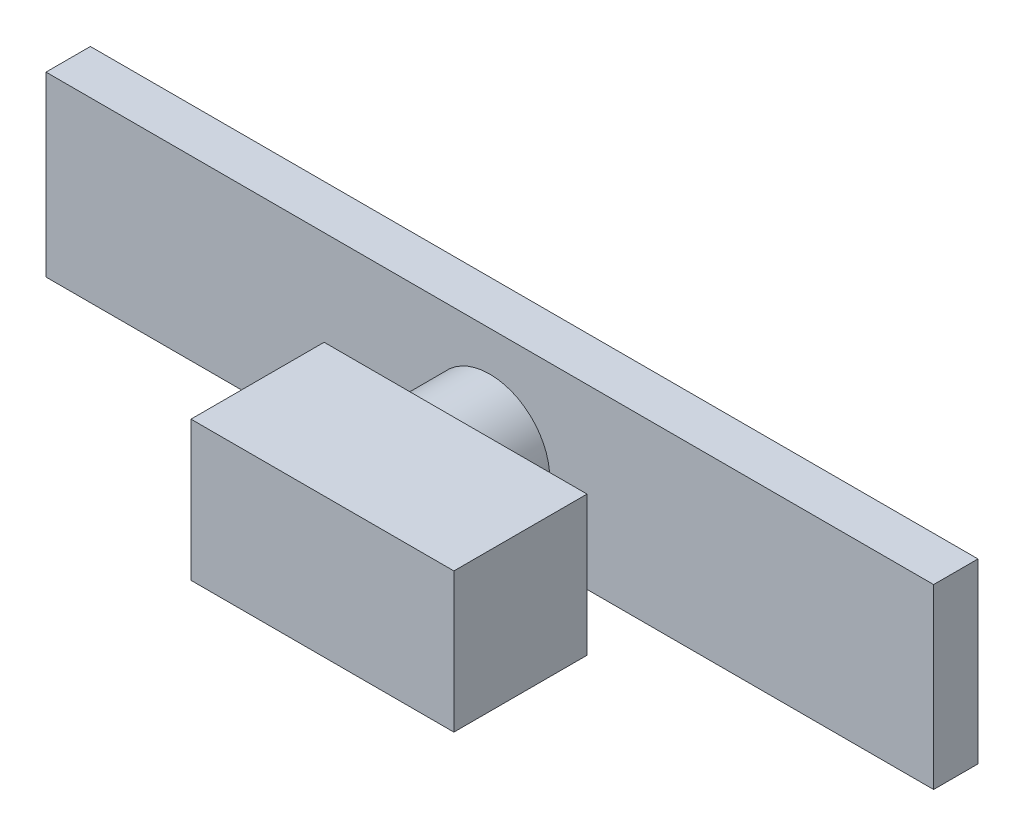
SolidWorks part; units mm, degrees
ref_plane "Front Plane" through (0, 0, 0) normal (0, 0, 1) x (1, 0, 0)
ref_plane "Top Plane" through (0, 0, 0) normal (0, 1, 0) x (1, 0, 0)
ref_plane "Right Plane" through (0, 0, 0) normal (1, 0, 0) x (0, 0, -1)
sketch "Sketch2" plane through (0, 0, 0) normal (0, 0, 1) x (1, 0, 0)
  line L1 (-47.8692, 21.2481) -> (206.1308, 21.2481)
  line L2 (-47.8692, 21.2481) -> (-47.8692, 8.5481)
  line L3 (-47.8692, 8.5481) -> (206.1308, 8.5481)
  line L4 (206.1308, 21.2481) -> (206.1308, 8.5481)
  dimension "D1" = 12.7
  dimension "D2" = 254
extrude "Boss-Extrude1" add sketch "Sketch2" along normal blind 50.8
sketch "Sketch3" plane through (0, 21.2481, 0) normal (0, 1, 0) x (1, 0, 0)
  circle A0 centre (79.1308, -28.4831) radius 17.1408
extrude "Boss-Extrude2" add sketch "Sketch3" along normal blind 19.05
sketch "Sketch4" plane through (0, 40.2981, 0) normal (0, 1, 0) x (1, 0, 0)
  line L1 (50.7675, -8.111) -> (126.0034, -8.111)
  line L2 (50.7675, -8.111) -> (50.7675, -48.0661)
  line L3 (50.7675, -48.0661) -> (126.0034, -48.0661)
  line L4 (126.0034, -8.111) -> (126.0034, -48.0661)
extrude "Boss-Extrude3" add sketch "Sketch4" along normal blind 38.1
scale "Scale2" scale about centroid uniform scaling yes scale factor 0.06
move or copy body "Body-Move/Copy1" bodies to move or copy 105 copy no rotation origin (0, 33.6669, 26.5501) rotation axis (1, 0, 0) rotation angle 90
move or copy body "Body-Move/Copy3" bodies to move or copy 106 copy no translate (-50.8, 0, -50.8)
scale "Scale5" scale about centroid uniform scaling yes scale factor 0.25
move or copy body "Body-Move/Copy9" bodies to move or copy 111 copy no translate (-50.8, 0, 0)
move or copy body "Body-Move/Copy13" bodies to move or copy 117 copy no translate (0, -50.8, 0)
scale "Scale6" bodies to scale 121 scale about centroid uniform scaling yes scale factor 0.25
